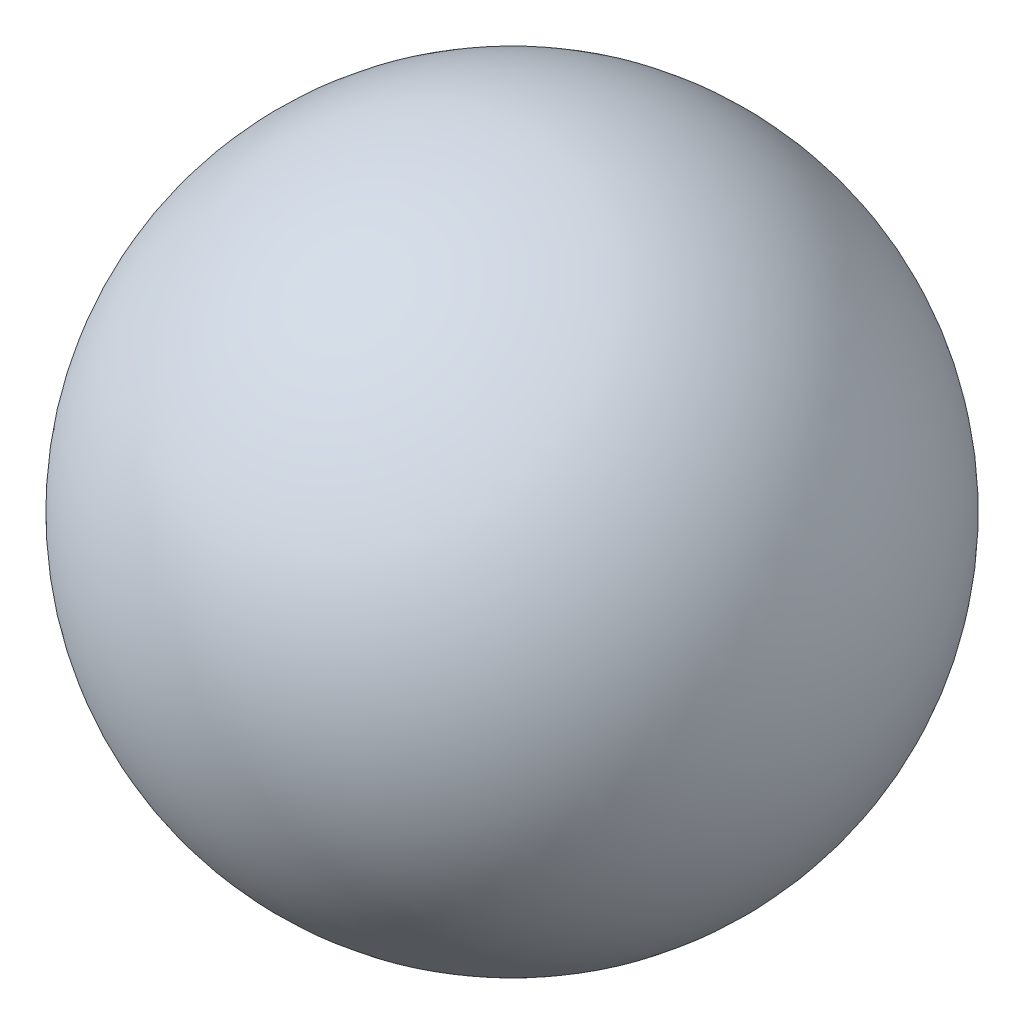
SolidWorks part; units mm, degrees
ref_plane "Plan de face" through (0, 0, 0) normal (0, 0, 1) x (1, 0, 0)
ref_plane "Plan de dessus" through (0, 0, 0) normal (0, 1, 0) x (1, 0, 0)
ref_plane "Plan de droite" through (0, 0, 0) normal (1, 0, 0) x (0, 0, -1)
sketch "Esquisse1" plane through (0, 0, 0) normal (0, 0, 1) x (1, 0, 0)
  line L0 (0, 20) -> (0, -20)
  arc A0 (0, -20) -> (0, 20) centre (0, 0) ccw
  dimension "D1" = 40
ref_axis "Axe1" through (0, -22, 0) along (0, 1, 0)
revolve "Révolution3" add sketch "Esquisse1" angle 360 about L0
